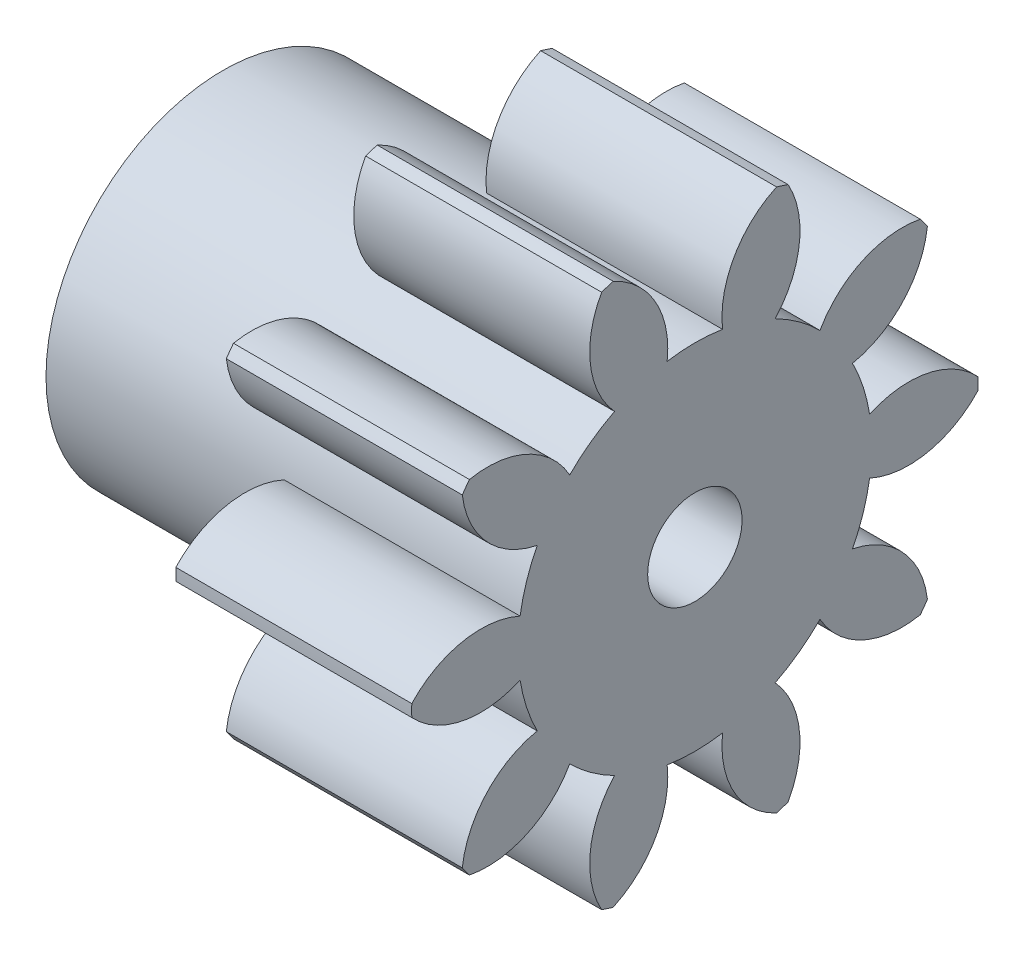
SolidWorks part; units mm, degrees
ref_plane "Plane1" through (0, 0, 0) normal (0, 0, 1) x (1, 0, 0)
ref_plane "Plane2" through (0, 0, 0) normal (0, 1, 0) x (1, 0, 0)
ref_plane "Plane3" through (0, 0, 0) normal (1, 0, 0) x (0, 0, -1)
sketch "HoldingSke" plane through (0, 0, 0) normal (0, 1, 0) x (1, 0, 0)
  line L0 (0, 0) -> (0.4924, -0.0868)
  line L1 (-15, 0) -> (100, 0) construction
  line L2 (0, 0) -> (-2.1039, 2.3779)
  line L3 (0, 0) -> (-11.863, 4.5341)
  line L4 (0, 0) -> (8.5048, 1.4996)
  line L5 (0, 0) -> (-18.7391, -6.9891)
  line L6 (0, 0) -> (-8.2896, -5.593)
  line L7 (-2.1039, 2.3779) -> (2.2011, 21.9091)
  line L8 (-76.2, 54.61) -> (-75.5, 54.61)
  line L9 (-71.009, 38.7566) -> (-53.1078, 45.2721)
  line L10 (-76.2, 71.12) -> (104.1128, 71.12)
  line L11 (0, 0) -> (-10, 0)
  line L12 (-76.2, 101.6) -> (-76.133, 101.6)
  line L13 (24.9733, 27.94) -> (52.9518, 28.4284)
  line L14 (24.9733, 27.94) -> (24.9743, 27.94)
  line L15 (24.9733, 27.94) -> (100.4006, 29.5858)
  line L16 (-63.627, -2) -> (-12.827, -2)
  circle A0 centre (0, 0) radius 2
  circle A1 centre (0, 0) radius 7.499
  circle A2 centre (0, 0) radius 25
  circle A3 centre (0, 0) radius 2
  dimension "MHD" = 14.998
  dimension "Hub_dia" = 50
  dimension "Bore" = 4
  dimension "MBD" = 4
  dimension "Num_teeth" = 10
  dimension "Pitch_radius" = 180.3128
  dimension "Pitch" = 0.5
  dimension "Width" = 10
  dimension "Overall_len" = 20
  dimension "Show_teeth" = 10
  dimension "Thickness" = 10
  dimension "OAL" = 20.0001
  dimension "T_dim" = 0.7
  dimension "Ap" = 20
  dimension "H" = 19.05
  dimension "Backlash" = 0.067
  dimension "Addendum_fac" = 1
  dimension "Dedendum_fac" = 1.25
  dimension "Clearance_fac" = 0.25
  dimension "Dedendum_add" = 0.001
  dimension "Module" = 2
sketch "BasProSke" plane through (0, 0, 0) normal (0, 1, 0) x (1, 0, 0)
  line L0 (-10, 0) -> (60, 0) construction
  line L1 (0, 0) -> (0, 12)
  line L2 (0, 0) -> (10, 0)
  line L3 (10, 0) -> (10, 12)
  line L4 (10, 12) -> (0, 12)
  dimension "Diameter" = 24
  dimension "Thickness" = 10
revolve "Base-Revolve" add sketch "BasProSke" angle 360 about L0
sketch "TooCutSke" plane through (0, 0, 0) normal (1, 0, 0) x (0, 0, -1)
  line L1 (0, 0) -> (0, 107) construction
  line L2 (0, 0) -> (-1.6814, 9.8576) construction
  line L3 (0, 0) -> (-6.1153, 18.8209) construction
  line L4 (-1.6814, 9.8576) -> (-3.0576, 9.4105) construction
  arc A0 (1.1737, 7.4066) -> (-1.1737, 7.4066) centre (0, 0) ccw
  arc A1 (3.4979, 11.5054) -> (-3.4979, 11.5054) centre (0, 0) ccw
  circle A2 centre (0, 0) radius 10 construction
  circle A3 centre (0, 0) radius 9.3969 construction
  arc A4 (-1.1737, 7.4066) -> (-3.4979, 11.5054) centre (-5.1477, 7.8615) ccw
  arc A5 (3.4979, 11.5054) -> (1.1737, 7.4066) centre (5.1477, 7.8615) ccw
  dimension "Root_dia" = 14.998
  dimension "Overcut_dia" = 24.0508
  dimension "Pitch_dia" = 20
  dimension "Base_dia" = 18.7939
  dimension "Flank_rad" = 4
  dimension "Half_ang" = 18
  dimension "Half_CT" = 1.4471
extrude "ToothCut" cut sketch "TooCutSke" along normal through all
fillet "Breaks" [suppressed] radius 0.04 tangent propagation no
fillet "RootFillets" [suppressed] radius 0.501
pattern_circular "TeethCuts" count 10 every 36 about axis through (-10, 0, 0) along (1, 0, 0) of "ToothCut", "RootFillets", "Breaks"
sketch "HubNeaOneSke" plane through (0, 0, 0) normal (-1, 0, 0) x (0, 0, 1)
  circle A0 centre (0, 0) radius 7.499
  dimension "Diameter" = 14.998
extrude "HubNearOne" add sketch "HubNeaOneSke" along normal blind 10.0001
sketch "HubNeaBotSke" plane through (0, 0, 0) normal (-1, 0, 0) x (0, 0, 1)
  circle A0 centre (0, 0) radius 7.499
  dimension "Diameter" = 14.998
extrude "HubNearBoth" [suppressed] add sketch "HubNeaBotSke" along normal blind 5
ref_plane "FarPln" through (10, 0, 0) normal (1, 0, 0) x (0, 0, -1)
sketch "HubFarSke" plane through (10, 0, 0) normal (1, 0, 0) x (0, 0, -1)
  circle A0 centre (0, 0) radius 7.499
  dimension "Diameter" = 14.998
extrude "HubFar" [suppressed] add sketch "HubFarSke" along normal blind 5
sketch "BorSke" plane through (0, 0, 0) normal (1, 0, 0) x (0, 0, -1)
  circle A0 centre (0, 0) radius 2
  dimension "Diameter" = 4
extrude "Bore" cut sketch "BorSke" along normal mid plane 40.0001
sketch "KeySke" plane through (0, 0, 0) normal (1, 0, 0) x (0, 0, -1)
  line L0 (-0.8, 0) -> (-0.8, 2.7)
  line L1 (-0.8, 2.7) -> (0.8, 2.7)
  line L2 (0.8, 2.7) -> (0.8, 0)
  line L3 (0, 0) -> (0, 34) construction
  line L4 (-0.8, 0) -> (0.8, 0)
  dimension "Offset" = 2.7
  dimension "Width" = 1.6
extrude "Keyway" [suppressed] cut sketch "KeySke" along normal mid plane 40.0001
pattern_circular "Keyway2" [suppressed] count 2 every 90 about axis through (-10, 0, 0) along (1, 0, 0)
ref_axis "Axe1" through (10, 0, 0) along (-1, 0, 0)
equation "' \"Module@HoldingSke\" = 6.35"
equation "' \"Num_teeth@HoldingSke\" = 12"
equation "' \"Ap@HoldingSke\" =  20"
equation "' \"Width@HoldingSke\" = 0.5 * 25.4"
equation "' \"Hub_dia@HoldingSke\"= 1 * 25.4"
equation "' \"Overall_len@HoldingSke\" = 1.0 * 25.4"
equation "' \"Bore@HoldingSke\" = 0.75 * 25.4"
equation "' \"T_dim@HoldingSke\" = 0.1 * 25.4"
equation "' \"Width@KeySke\" = 0.25 * 25.4"
equation "' \"Show_teeth@HoldingSke\" = 13"
equation "' \"Backlash@HoldingSke\" = 0.009 * 25.4"
equation "' \"Addendum_fac@HoldingSke\" = 1.0"
equation "' \"Dedendum_fac@HoldingSke\" = 1.25"
equation "' \"Dedendum_add@HoldingSke\" = 0.00005 * 25.4"
equation "' \"Clearance_fac@HoldingSke\" = 0.25"
equation "\"Pitch@HoldingSke\" = 1 / \"Module@HoldingSke\""
equation "\"Overcut_dia@TooCutSke\" = (\"Num_teeth@HoldingSke\" + 2 * \"Addendum_fac@HoldingSke\") / \"Pitch@HoldingSke\" + 0.002 * 25.4"
equation "\"Pitch_dia@TooCutSke\" = \"Num_teeth@HoldingSke\" / \"Pitch@HoldingSke\""
equation "\"Base_dia@TooCutSke\" = \"Num_teeth@HoldingSke\" / \"Pitch@HoldingSke\" * cos((\"Ap@HoldingSke\"  * 3.14159265 / 180))"
equation "\"Root_dia@TooCutSke\" = (\"Num_teeth@HoldingSke\" + 2) / \"Pitch@HoldingSke\" - 2 * (\"Addendum_fac@HoldingSke\" + \"Dedendum_fac@HoldingSke\") / \"Pitch@HoldingSke\" - \"Dedendum_add@HoldingSke\" * 2"
equation "\"Half_ang@TooCutSke\" = 180 / \"Num_teeth@HoldingSke\""
equation "\"Half_CT@TooCutSke\" = \"Num_teeth@HoldingSke\" / \"Pitch@HoldingSke\" * sin((3.14159265 / 2 / \"Num_teeth@HoldingSke\")) / 2 - 7 * \"Backlash@HoldingSke\" / 4"
equation "\"Flank_rad@TooCutSke\" = \"Num_teeth@HoldingSke\" / \"Pitch@HoldingSke\" / 5"
equation "\"Radius@RootFillets\" = \"Clearance_fac@HoldingSke\" / \"Pitch@HoldingSke\" + \"Dedendum_add@HoldingSke\""
equation "\"Break_rad@Breaks\" = 0.02 / \"Pitch@HoldingSke\""
equation "\"Thickness@HoldingSke\" = \"Width@HoldingSke\""
equation "\"OAL@HoldingSke\" = \"Thickness@HoldingSke\""
equation "\"MHD@HoldingSke\" = (\"Num_teeth@HoldingSke\" + 2) / \"Pitch@HoldingSke\" - 2 * (\"Addendum_fac@HoldingSke\" + \"Dedendum_fac@HoldingSke\")  / \"Pitch@HoldingSke\" - \"Dedendum_add@HoldingSke\" * 2"
equation "\"MBD@HoldingSke\" = (\"Num_teeth@HoldingSke\" + 2) / \"Pitch@HoldingSke\" - 2 * (\"Addendum_fac@HoldingSke\" + \"Dedendum_fac@HoldingSke\")  / \"Pitch@HoldingSke\" - \"Dedendum_add@HoldingSke\" * 2 - 0.002 * 25.4"
equation "\"MHD@HoldingSke\" = ((sgn( \"MHD@HoldingSke\" - \"Hub_dia@HoldingSke\" )-1)*( \"MHD@HoldingSke\" - \"Hub_dia@HoldingSke\" ))/-2+ \"Hub_dia@HoldingSke\""
equation "\"MBD@HoldingSke\" = ((sgn( \"MBD@HoldingSke\" - \"Bore@HoldingSke\" )-1)*( \"MBD@HoldingSke\" - \"Bore@HoldingSke\" ))/-2+ \"Bore@HoldingSke\""
equation "\"OAL@HoldingSke\" = ((sgn( \"OAL@HoldingSke\" - \"Overall_len@HoldingSke\" )+1)*( \"OAL@HoldingSke\" - \"Overall_len@HoldingSke\" ))/2 + \"Overall_len@HoldingSke\" + 0.000002 * 25.4"
equation "\"Num_teeth@TeethCuts\" = int( \"Show_teeth@HoldingSke\" ) + 1"
equation "\"Num_teeth@TeethCuts\" = ((sgn( \"Num_teeth@TeethCuts\" - \"Num_teeth@HoldingSke\" )-1)*( \"Num_teeth@TeethCuts\" - \"Num_teeth@HoldingSke\" ))/-2+ \"Num_teeth@HoldingSke\""
equation "\"Num_teeth@TeethCuts\" = ((sgn( \"Num_teeth@TeethCuts\" - 2.0)+1)*( \"Num_teeth@TeethCuts\" - 2.0))/2 +2.0"
equation "\"Angle@TeethCuts\" = 360.0 / \"Num_teeth@HoldingSke\""
equation "\"Diameter@BasProSke\" = (\"Num_teeth@HoldingSke\" + 2 * \"Addendum_fac@HoldingSke\") / \"Pitch@HoldingSke\""
equation "\"Thickness@BasProSke\"  = \"Thickness@HoldingSke\""
equation "' \"Fillet_rad@BasProSke\" =  \"Thickness@HoldingSke\" * 0.05"
equation "\"MHD@HoldingSke\" = ((sgn( \"MHD@HoldingSke\" - \"Root_dia@TooCutSke\" )-1)*( \"MHD@HoldingSke\" - \"Root_dia@TooCutSke\" ))/-2+ \"Root_dia@TooCutSke\""
equation "\"Diameter@HubNeaOneSke\" = \"MHD@HoldingSke\""
equation "\"Length@HubNearOne\" = \"OAL@HoldingSke\" - \"Thickness@BasProSke\""
equation "\"Diameter@HubNeaBotSke\" = \"MHD@HoldingSke\""
equation "\"Length@HubNearBoth\" = ( \"OAL@HoldingSke\" - \"Thickness@BasProSke\" ) / 2.0"
equation "\"Thickness@FarPln\" = \"Thickness@BasProSke\""
equation "\"Diameter@HubFarSke\" = \"MHD@HoldingSke\""
equation "\"Length@HubFar\" = ( \"OAL@HoldingSke\" - \"Thickness@BasProSke\" ) / 2.0"
equation "\"Diameter@BorSke\" = \"MBD@HoldingSke\""
equation "\"D1@Bore\" = \"OAL@HoldingSke\" * 2.0"
equation "\"D1@Keyway\" = \"OAL@HoldingSke\" * 2.0"
equation "\"Offset@KeySke\" = \"T_dim@HoldingSke\" + \"MBD@HoldingSke\" / 2.0"
